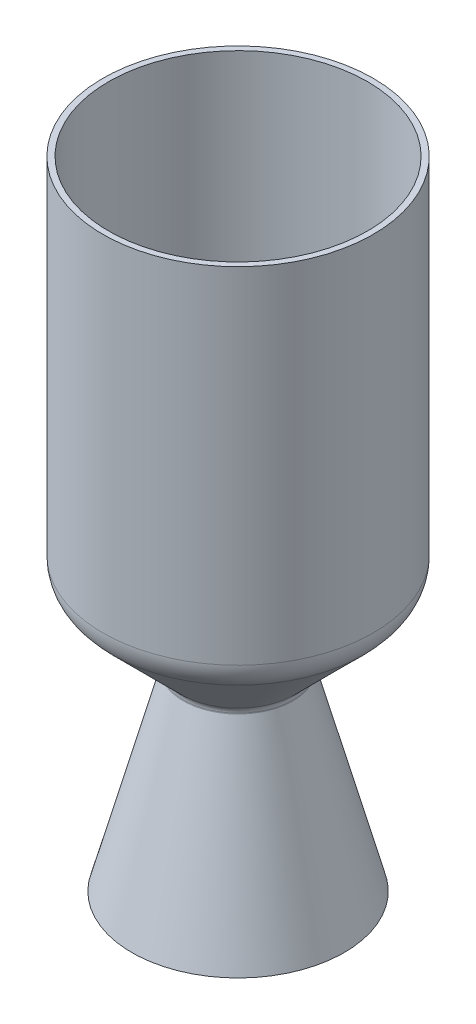
SolidWorks part; units mm, degrees
note: '?' marks a value the reader was unsure of.
ref_plane "Front Plane" through (0, 0, 0) normal (0, 0, 1) x (1, 0, 0)
ref_plane "Top Plane" through (0, 0, 0) normal (0, 1, 0) x (1, 0, 0)
ref_plane "Right Plane" through (0, 0, 0) normal (1, 0, 0) x (0, 0, -1)
sketch "Sketch1" plane through (0, 0, 0) normal (0, 0, 1) x (1, 0, 0)
  line L0 (0, 0) -> (0, 24.9897) construction
  line L1 (-57.15, 195.8508) -> (-57.15, 43.4508)
  line L2 (-53.4303, 34.4705) -> (-23.4499, 4.4901)
  line L3 (-21.7198, -0.9861) -> (-44.45, -85.8163)
  line L4 (-6.35, 106.0779) -> (-6.35, 91.3255) construction
  arc A0 (-57.15, 43.4508) -> (-53.4303, 34.4705) centre (-44.45, 43.4508) ccw
  arc A1 (-23.4499, 4.4901) -> (-21.59, 0) centre (-27.94, 0) cw
  arc A2 (-21.59, 0) -> (-21.7198, -0.9861) centre (-25.4, 0) cw
  dimension "D2" = 12.7
  dimension "D5" = 3.81
  dimension "D6" = 6.35
  dimension "D1" = 45
  dimension "D3" = 152.4
  dimension "D4" = 15
  dimension "D7" = 6.35
  dimension "D8" = 15.24
  dimension "D9" = 50.8
  dimension "D10" = 38.1
  dimension "D11" = 45
revolve "Revolve-Thin1" add sketch "Sketch1" angle 360 about L0
ref_plane "Plane1" through (0, 195.8508, 0) normal (0, 1, 0) x (1, 0, 0)
ref_plane "Plane2" through (0, 43.4508, 0) normal (0, -1, 0) x (-1, 0, 0)
ref_plane "Plane3" through (0, -85.1589, 0) normal (0, 1, 0) x (1, 0, 0)
ref_axis "Axis1" through (0, 209.9342, 0) along (0, -1, 0)?
